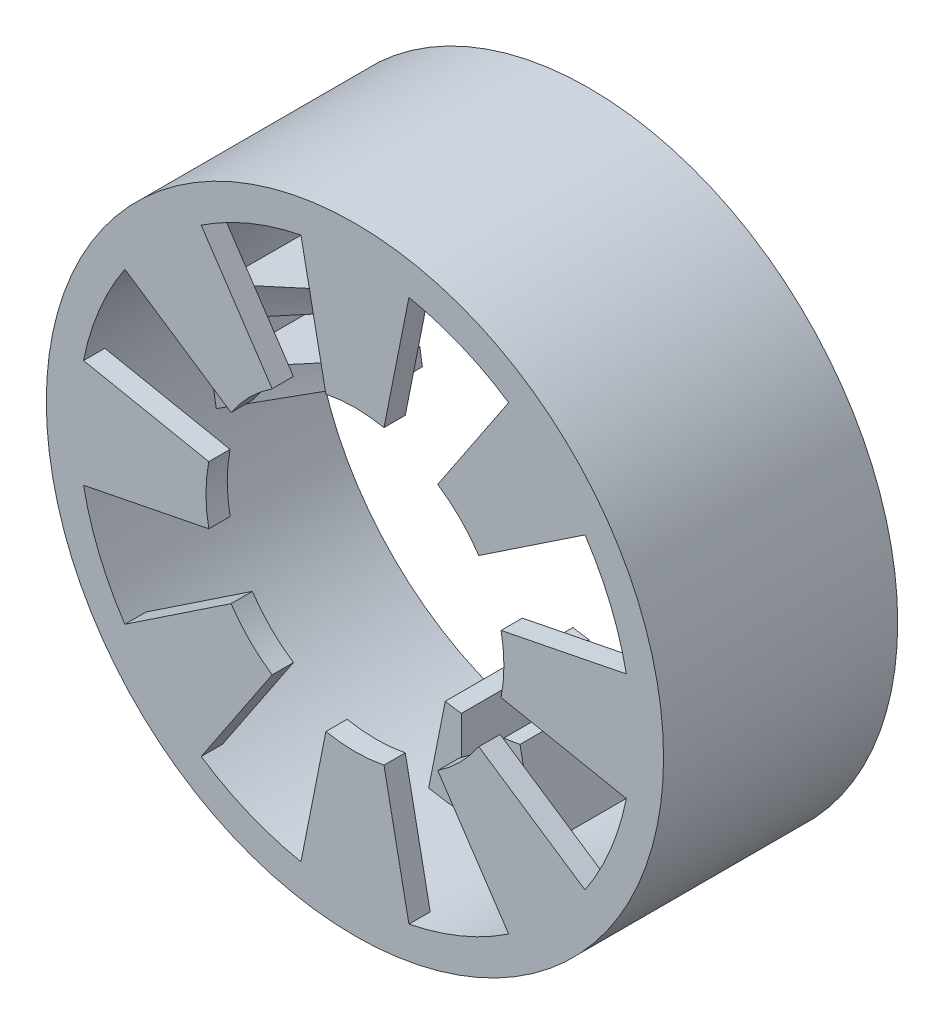
SolidWorks part; units mm, degrees
ref_plane "Front Plane" through (0, 0, 0) normal (0, 0, 1) x (1, 0, 0)
ref_plane "Top Plane" through (0, 0, 0) normal (0, 1, 0) x (1, 0, 0)
ref_plane "Right Plane" through (0, 0, 0) normal (1, 0, 0) x (0, 0, -1)
sketch "Sketch1" plane through (0, 0, 0) normal (0, 0, 1) x (1, 0, 0)
  line L0 (0, 0) -> (0, 23.0788) construction
  line L1 (2.5362, 12.7502) -> (1.3656, 6.8655)
  line L2 (-2.5362, 12.7502) -> (-1.3656, 6.8655)
  line L3 (10.8091, 7.2224) -> (5.8203, 3.889)
  line L4 (7.2224, 10.8091) -> (3.889, 5.8203)
  line L5 (12.7502, -2.5362) -> (6.8655, -1.3656)
  line L6 (12.7502, 2.5362) -> (6.8655, 1.3656)
  line L7 (7.2224, -10.8091) -> (3.889, -5.8203)
  line L8 (10.8091, -7.2224) -> (5.8203, -3.889)
  line L9 (-2.5362, -12.7502) -> (-1.3656, -6.8655)
  line L10 (2.5362, -12.7502) -> (1.3656, -6.8655)
  line L11 (-10.8091, -7.2224) -> (-5.8203, -3.889)
  line L12 (-7.2224, -10.8091) -> (-3.889, -5.8203)
  line L13 (-12.7502, 2.5362) -> (-6.8655, 1.3656)
  line L14 (-12.7502, -2.5362) -> (-6.8655, -1.3656)
  line L15 (-7.2224, 10.8091) -> (-3.889, 5.8203)
  line L16 (-10.8091, 7.2224) -> (-5.8203, 3.889)
  circle A0 centre (0, 0) radius 14.5
  circle A1 centre (0, 0) radius 13
  circle A2 centre (0, 0) radius 7
  point P41 (0, 0)
  dimension "D1" = 29
  dimension "D2" = 26
  dimension "D3" = 14
  dimension "D4" = 11.25
  dimension "D5" = 11.25
  dimension "D6" = 8
extrude "Boss-Extrude1" add sketch "Sketch1" along normal blind 1 contours A1 A0 | A2 L15 A1 L16 | L0 A2 L1 A1 | A2 L0 A1 L2 | A2 L3 A1 L4 | A2 L5 A1 L6 | A2 L7 A1 L8 | A2 L9 A1 L10 | A2 L11 A1 L12 | A2 L13 A1 L14 region at (-1.008, 10.2339, 0) region at (1.008, 10.2339, 0) region at (9.963, 9.963, 0) region at (7.2365, 7.2365, 0) region at (-7.2365, 7.2365, 0) region at (10.2339, 0, 0) region at (-10.2339, 0, 0) region at (-7.2365, -7.2365, 0) region at (7.2365, -7.2365, 0) region at (0, -10.2339, 0)
ref_plane "Plane1" through (0, 0, -5) normal (0, 0, 1) x (1, 0, 0)
sketch "Sketch2" plane through (0, 0, -5) normal (0, 0, -1) x (-1, 0, 0)
  line L0 (0, 0) -> (0, 17.7378) construction
  line L1 (1.2681, 6.3751) -> (2.5362, 12.7502)
  line L2 (-1.2681, 6.3751) -> (-2.5362, 12.7502)
  line L3 (6.3751, -1.2681) -> (12.7502, -2.5362)
  line L4 (1, 6.4226) -> (1, 12.9615)
  line L5 (6.3751, 1.2681) -> (12.7502, 2.5362)
  line L6 (-1, 12.9615) -> (-1, 6.4226)
  line L7 (6.4226, -1) -> (12.9615, -1)
  line L8 (12.9615, 1) -> (6.4226, 1)
  line L9 (-1.2681, -6.3751) -> (-2.5362, -12.7502)
  line L10 (1.2681, -6.3751) -> (2.5362, -12.7502)
  line L11 (-1, -6.4226) -> (-1, -12.9615)
  line L12 (1, -12.9615) -> (1, -6.4226)
  line L13 (-6.3751, 1.2681) -> (-12.7502, 2.5362)
  line L14 (-6.3751, -1.2681) -> (-12.7502, -2.5362)
  line L15 (-6.4226, 1) -> (-12.9615, 1)
  line L16 (-12.9615, -1) -> (-6.4226, -1)
  circle A0 centre (0, 0) radius 14.5
  arc A1 (1.2681, 6.3751) -> (-1.2681, 6.3751) centre (0, 0) ccw
  circle A2 centre (0, 0) radius 13
  arc A3 (6.3751, -1.2681) -> (6.3751, 1.2681) centre (0, 0) ccw
  circle A4 centre (0, 0) radius 9
  arc A5 (-1.2681, -6.3751) -> (1.2681, -6.3751) centre (0, 0) ccw
  arc A7 (-6.3751, 1.2681) -> (-6.3751, -1.2681) centre (0, 0) ccw
  point P39 (0, 0)
  dimension "D1" = 29
  dimension "D4" = 13
  dimension "D7" = 26
  dimension "D9" = 18
  dimension "D2" = 11.25
  dimension "D3" = 11.25
  dimension "D5" = 1
  dimension "D6" = 1
  dimension "D8" = 4
extrude "Boss-Extrude2" add sketch "Sketch2" along normal blind 6 contours L1 A4 L4 A2 | L6 A4 L2 A2 | L13 A4 L15 A2 | L16 A4 L14 A2 | L9 A4 L11 A2 | L12 A4 L10 A2 | L3 A4 L7 A2 | L8 A4 L5 A2 region at (-1.5966, 11.1066, -5) region at (-11.1066, 1.5966, -5) region at (1.5966, 11.1066, -5) region at (-11.1066, -1.5966, -5) region at (11.1066, 1.5966, -5) region at (-1.5966, -11.1066, -5) region at (11.1066, -1.5966, -5) region at (1.5966, -11.1066, -5)
sketch "Sketch3" plane through (0, 0, 0) normal (0, 0, -1) x (-1, 0, 0)
  circle A0 centre (0, 0) radius 13
  circle A1 centre (0, 0) radius 14.5
  dimension "D1" = 26
  dimension "D2" = 29
extrude "Boss-Extrude3" add sketch "Sketch3" along normal blind 10
chamfer "Chamfer1" distance 5 angle 40 1 edges at (-8.8937, -1.3792, -5) first distance on face at (-8.8897, -1.3785, -8)
chamfer "Chamfer2" distance 5 angle 40 1 edges at (-8.8937, 1.3792, -5) first distance on face at (-8.8897, 1.3785, -8)
